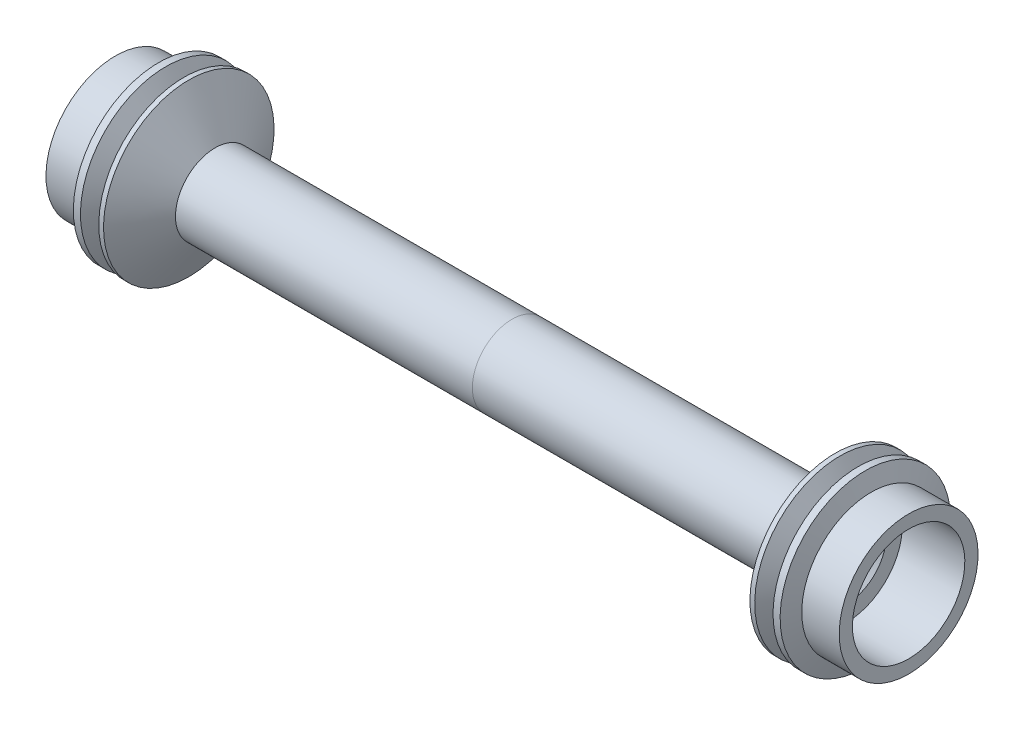
SolidWorks part; units mm, degrees
ref_plane "Front Plane" through (0, 0, 0) normal (0, 0, 1) x (1, 0, 0)
ref_plane "Top Plane" through (0, 0, 0) normal (0, 1, 0) x (1, 0, 0)
ref_plane "Right Plane" through (0, 0, 0) normal (1, 0, 0) x (0, 0, -1)
sketch "Sketch2" plane through (0, 0, 0) normal (0, 0, 1) x (1, 0, 0)
  line L0 (0, 0) -> (0, 28.4375) construction
  line L1 (-31.75, 4.5) -> (-26.75, 4.5) construction
  line L2 (-31.75, 4.5) -> (-31.75, -4.5) construction
  line L3 (-31.75, -4.5) -> (-26.75, -4.5) construction
  line L4 (-26.75, 4.5) -> (-26.75, -4.5) construction
  line L5 (-31.75, 4.5) -> (-26.75, -4.5) construction
  line L6 (-31.75, -4.5) -> (-26.75, 4.5) construction
  line L7 (26.75, 4.5) -> (36.8332, 4.5) construction
  line L8 (26.75, 4.5) -> (26.75, -4.5) construction
  line L9 (26.75, -4.5) -> (36.8332, -4.5) construction
  line L10 (36.8332, 4.5) -> (36.8332, -4.5) construction
  line L11 (26.75, 4.5) -> (36.8332, -4.5) construction
  line L12 (26.75, -4.5) -> (36.8332, 4.5) construction
  line L13 (-31.75, 0) -> (36.8332, 0) construction
  line L14 (-31.75, 5.5562) -> (-28.75, 5.5562)
  line L15 (-28.75, 5.5562) -> (-28.2878, 6.8262)
  line L16 (-28.2878, 6.8262) -> (-27.7207, 6.8262)
  line L17 (-27.7207, 6.8262) -> (-26.9875, 5.5562)
  line L18 (-26.9875, 5.5562) -> (-26.2543, 6.8262)
  line L19 (-26.2543, 6.8262) -> (-25.8733, 6.8262)
  line L20 (-25.8733, 6.8262) -> (-23.7652, 3.175)
  line L21 (-23.7652, 3.175) -> (0, 3.175)
  line L22 (-31.75, 5.5562) -> (-31.75, 4.5)
  line L23 (-31.75, 4.5) -> (-26.75, 4.5)
  line L24 (-26.75, 4.5) -> (-26.75, 0)
  line L25 (-26.75, 0) -> (0, 0)
  line L26 (0, 0) -> (0, 3.175)
  line L27 (-33.5594, -5.5562) -> (-33.5594, 5.5562) construction
  line L28 (-26.9875, 5.5562) -> (-26.9875, 7.68) construction
  line L29 (-26.9875, 5.5562) -> (26.9875, 5.5562) construction
  line L30 (-31.75, 5.5562) -> (31.75, 5.5562) construction
  line L31 (0, 1.6) -> (-12.5, 1.6)
  line L32 (-12.5, 1.6) -> (-14.1, 0)
  line L33 (-12.5, 1.6) -> (-12.5, -1.6) construction
  line L34 (-12.5, 1.6) -> (12.5, 1.6) construction
  line L35 (-26.75, 1.7145) -> (-21.925, 1.7145)
  line L36 (-21.925, 1.7145) -> (-21.925, 0)
  line L37 (-26.75, 3.23) -> (-26.242, 2.722)
  line L38 (-21.925, 1.7145) -> (-34.925, 1.7145) construction
  line L39 (-21.925, 1.7145) -> (-21.925, -1.7145) construction
  line L40 (-21.925, -1.7145) -> (-34.925, -1.7145) construction
  line L41 (-34.925, 1.7145) -> (-34.925, -1.7145) construction
  line L42 (-26.242, 2.722) -> (-26.242, 0)
  point P0 (-29.25, 0)
  point P5 (31.7916, 0)
  point P27 (-33.5594, 0)
  point P28 (-26.0638, 6.8262)
  point P29 (-12.5, 0)
  point P31 (37.1027, 5.5562)
  point P33 (0, 5.5562)
  point P36 (0, 1.6)
  point P48 (-21.925, 0)
  point P51 (0, 5.5562)
  point P52 (36.0232, 5.5562)
  dimension "D1" = 5
  dimension "D3" = 3.175
  dimension "D4" = 11.1125
  dimension "D5" = 9
  dimension "D6" = 60
  dimension "D7" = 60
  dimension "D8" = 1.27
  dimension "D9" = 70
  dimension "D10" = 53.975
  dimension "D11" = 63.5
  dimension "D12" = 0.381
  dimension "D13" = 45
  dimension "D14" = 25
  dimension "D15" = 3.2
  dimension "D16" = 3.429
  dimension "D17" = 3.175
  dimension "D18" = 1.27
  dimension "D19" = 0.508
  dimension "D20" = 45
  dimension "D21" = 13
  dimension "D22" = 3
revolve "Revolve1" add sketch "Sketch2" angle 360 about L13 region at (-16.7946, 2.5868, 0)
mirror "Mirror1" about plane through (0, 0, 0) normal (1, 0, 0) of bodies 101
chamfer "Chamfer1" distance 0.508 angle 45 1 edges at (-31.75, -4.5, 0)
